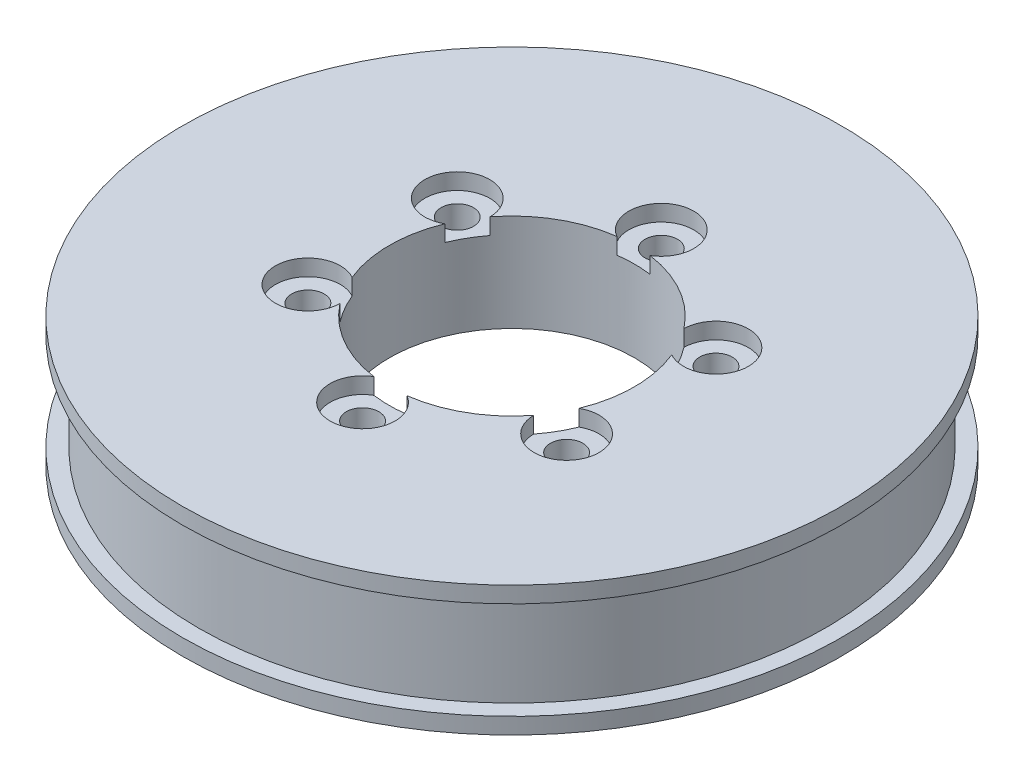
SolidWorks part; units mm, degrees
material "ABS"
ref_plane "Front Plane" through (0, 0, 0) normal (0, 0, 1) x (1, 0, 0)
ref_plane "Top Plane" through (0, 0, 0) normal (0, 1, 0) x (1, 0, 0)
ref_plane "Right Plane" through (0, 0, 0) normal (1, 0, 0) x (0, 0, -1)
sketch "Sketch2" plane through (0, 0, 0) normal (0, 1, 0) x (1, 0, 0)
  circle A0 centre (0, 0) radius 21.3
  circle A1 centre (0, 0) radius 19.3
  circle A2 centre (0, 0) radius 17.8
  circle A3 centre (0, 0) radius 20.3
  dimension "D1" = 42.6
  dimension "D2" = 2
  dimension "D3" = 1.5
  dimension "D4" = 1
extrude "Boss-Extrude1" add sketch "Sketch2" along normal blind 8 contours A1 A2 region at (-18.7541, 0, 0)
extrude "Boss-Extrude2" add sketch "Sketch2<3>" along normal blind 1 contours A3 A1 region at (-19.7258, 0, 0)
sketch "Sketch2<3>" plane through (0, 0, 0) normal (0, 1, 0) x (1, 0, 0) same geometry as "Sketch2"
extrude "Boss-Extrude3" add sketch "Sketch2<4>" against normal blind 1 from surface contours A3 A1 region at (-19.7258, 0, 0) starting at face at (0, 8, 17.8)
sketch "Sketch2<4>" plane through (0, 0, 0) normal (0, 1, 0) x (1, 0, 0) same geometry as "Sketch2"
sketch "Sketch3" plane through (0, 8, 0) normal (0, 1, 0) x (1, 0, 0)
  circle A0 centre (0, 0) radius 17.8
  circle A1 centre (0, 0) radius 7.55
  dimension "D1" = 15.1
extrude "Boss-Extrude4" add sketch "Sketch3" against normal blind 2
sketch "Sketch4" plane through (0, 6, 0) normal (0, -1, 0) x (1, 0, 0)
  circle A0 centre (0, 0) radius 7.55
  circle A1 centre (0, 0) radius 11.25
  circle A2 centre (0, 9.2) radius 1
  circle A5 centre (0, 0) radius 7.55 construction
  circle A6 centre (7.9674, 4.6) radius 1
  circle A7 centre (7.9674, -4.6) radius 1
  circle A8 centre (0, -9.2) radius 1
  circle A9 centre (-7.9674, -4.6) radius 1
  circle A10 centre (-7.9674, 4.6) radius 1
  dimension "D1" = 22.5
  dimension "D2" = 2
  dimension "D3" = 9.2
  dimension "D5" = 9.2
  dimension "D4" = 6
extrude "Boss-Extrude5" add sketch "Sketch4" along normal blind 4
sketch "Sketch5" plane through (0, 2, 0) normal (0, -1, 0) x (1, 0, 0)
  circle A3 centre (0, 9.2) radius 1
  circle A4 centre (0, 9.2) radius 1 construction
  circle A5 centre (7.9674, 4.6) radius 1
  circle A6 centre (7.9674, -4.6) radius 1
  circle A7 centre (0, -9.2) radius 1
  circle A8 centre (-7.9674, -4.6) radius 1
  circle A9 centre (-7.9674, 4.6) radius 1
  dimension "D2" = 9.2
  dimension "D1" = 6
extrude "Cut-Extrude1" cut sketch "Sketch5" against normal up to surface (6 mm away) up to face at (0, 8, 20.3)
sketch "Sketch6" plane through (0, 8, 0) normal (0, 1, 0) x (1, 0, 0)
  circle A2 centre (0, -9.2) radius 2
  circle A3 centre (-7.9674, -4.6) radius 2
  circle A4 centre (-7.9674, 4.6) radius 2
  circle A5 centre (0, 9.2) radius 2
  circle A6 centre (7.9674, 4.6) radius 2
  circle A7 centre (7.9674, -4.6) radius 2
  dimension "D1" = 4
  dimension "D2" = 6
  dimension "D3" = 9.2
extrude "Cut-Extrude2" cut sketch "Sketch6" against normal blind 1
fillet "Fillet1" radius 2 2 edges at (0, 6, 11.25) (0, 6, 17.8) conic rho 0.16
